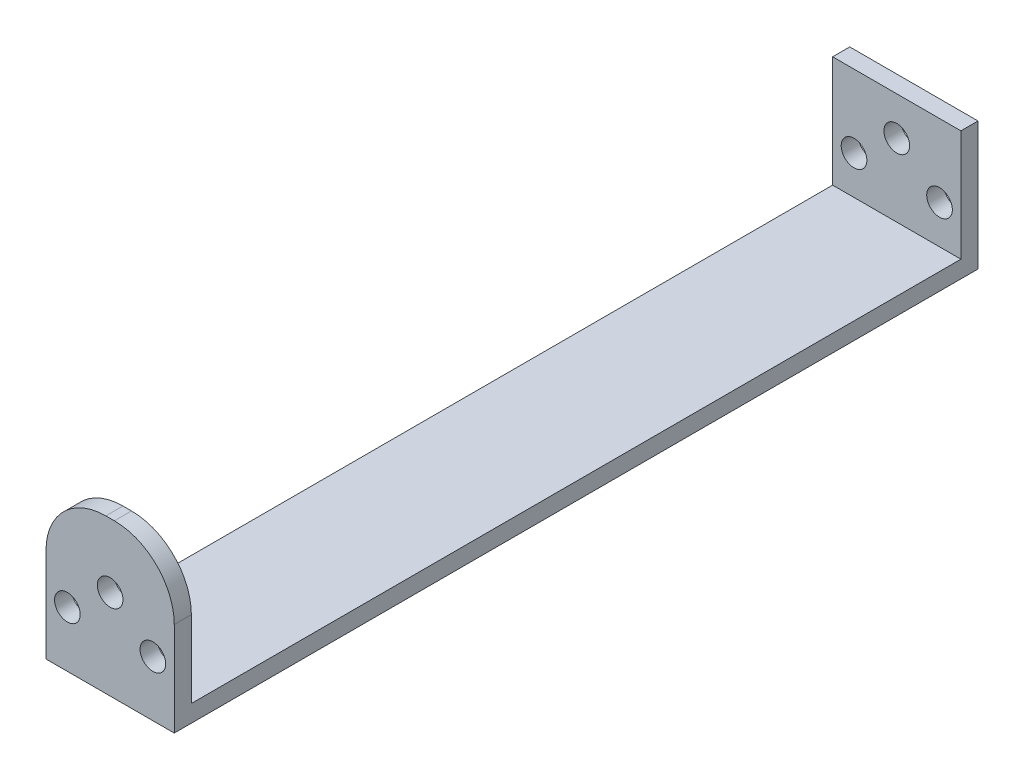
SolidWorks part; units mm, degrees
ref_plane "Alzado" through (0, 0, 0) normal (0, 0, 1) x (1, 0, 0)
ref_plane "Planta" through (0, 0, 0) normal (0, 1, 0) x (1, 0, 0)
ref_plane "Vista lateral" through (0, 0, 0) normal (1, 0, 0) x (0, 0, -1)
sketch "Croquis1" plane through (0, 0, 0) normal (1, 0, 0) x (0, 0, -1)
  line L0 (-47, 13) -> (-47, -2)
  line L1 (-45, 13) -> (45, 13) construction
  line L2 (-45, 13) -> (-45, 0)
  line L3 (-45, 0) -> (45, 0)
  line L4 (45, 13) -> (45, 0)
  line L5 (-47, -2) -> (47, -2)
  line L6 (47, 13) -> (47, -2)
  line L9 (45, 13) -> (47, 13)
  line L11 (-47, 15) -> (-47, -2) construction
  line L12 (-47, 15) -> (47, 15) construction
  line L13 (47, 15) -> (47, -2) construction
  line L14 (-45, 13) -> (-47, 13) construction
  line L15 (-45, 13) -> (-45, 16)
  line L16 (-45, 16) -> (-47, 16)
  line L17 (-47, 13) -> (-47, 16)
  point P4 (0, 0)
  dimension "D1" = 90
  dimension "D3" = 15
  dimension "D4" = 18
  dimension "D2" = 2
extrude "Saliente-Extruir1" add sketch "Croquis1" along normal mid plane 15
sketch "Croquis2" plane through (0, 0, 0) normal (0, 0, 1) x (1, 0, 0)
  line L0 (0, 8.5) -> (0, 0) construction
  line L1 (7.5, -2) -> (-7.5, -2) construction
  circle A0 centre (0, 8.5) radius 1.5
  circle A1 centre (5, 4.5) radius 1.5
  circle A2 centre (-5, 4.5) radius 1.5
  point P6 (0, 10)
  dimension "D1" = 3
  dimension "D2" = 3
  dimension "D5" = 10
  dimension "D3" = 12
  dimension "D4" = 4
extrude "Cortar-Extruir1" cut sketch "Croquis2" against normal through all both and the other way through all
fillet "Redondeo1" radius 7 2 edges at (7.5, 16, 46) (-7.5, 16, 46)
